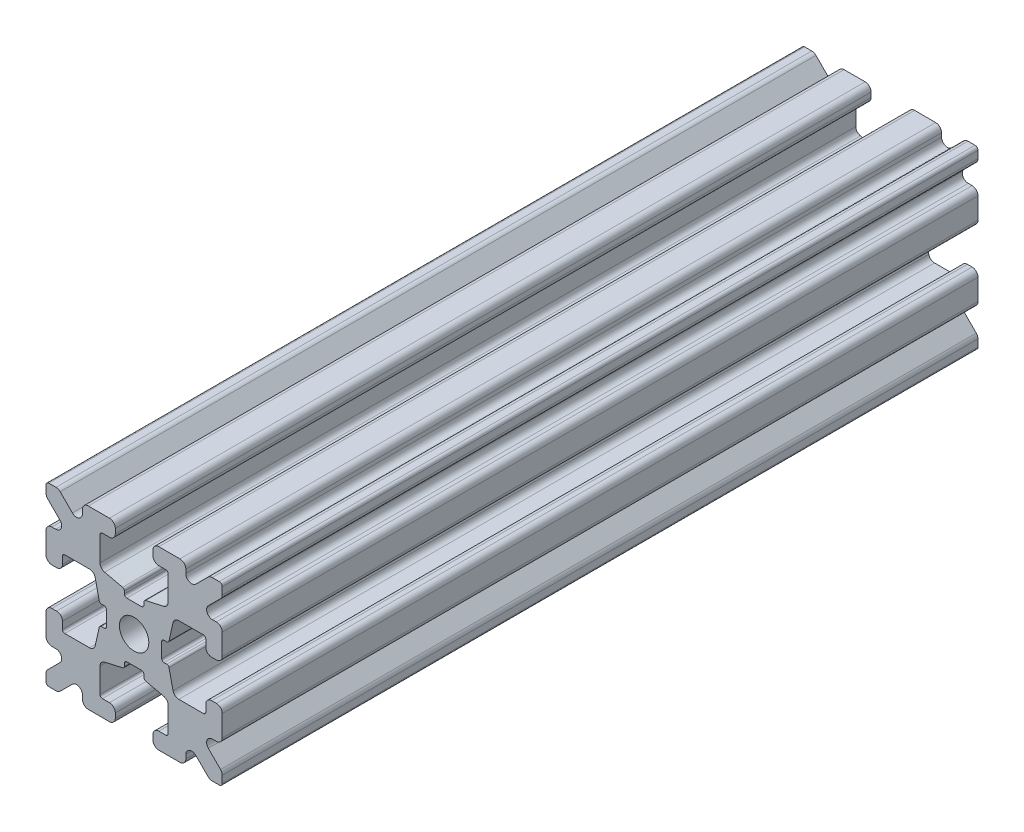
SolidWorks part; units mm, degrees
ref_plane "Front Plane" through (0, 0, 0) normal (0, 0, 1) x (1, 0, 0)
ref_plane "Top Plane" through (0, 0, 0) normal (0, 1, 0) x (1, 0, 0)
ref_plane "Right Plane" through (0, 0, 0) normal (1, 0, 0) x (0, 0, -1)
sketch "Sketch1" plane through (0, 0, 0) normal (0, 0, 1) x (1, 0, 0)
  line L1 (-7.5, -7.5) -> (7.5, -7.5)
  line L2 (-7.5, -7.5) -> (-7.5, 7.5)
  line L3 (-7.5, 7.5) -> (7.5, 7.5)
  line L4 (7.5, -7.5) -> (7.5, 7.5)
  line L5 (-7.5, -7.5) -> (7.5, 7.5) construction
  line L6 (-7.5, 7.5) -> (7.5, -7.5) construction
  circle A0 centre (0, 0) radius 1.25
  point P0 (0, 0)
  dimension "D2" = 2.5
  dimension "D1" = 15
extrude "Boss-Extrude1" add sketch "Sketch1" along normal mid plane 64.328
fillet "Fillet1" radius 0.25 4 edges at (7.5, -7.5, 0) (-7.5, -7.5, 0) (7.5, 7.5, 0) (-7.5, 7.5, 0)
sketch "Sketch2" plane through (0, 0, 32.164) normal (0, 0, 1) x (1, 0, 0)
  line L0 (-7.5, 7.25) -> (-7.5, -7.25) construction
  line L1 (-7.5, 1.6) -> (-6.1, 1.6)
  line L2 (-7.5, 1.6) -> (-7.5, -1.6)
  line L3 (-7.5, -1.6) -> (-6.1, -1.6)
  line L4 (-6.1, 1.6) -> (-6.1, 2.9)
  line L5 (0, 0) -> (-12.1036, 0) construction
  line L6 (-6.1, -2.9) -> (-3.4, -2.9)
  line L7 (0, 0) -> (-7.25, 7.25) construction
  line L8 (-6.1, 2.9) -> (-3.4, 2.9)
  line L9 (-3.4, -2.9) -> (-3.4, 2.9)
  line L10 (55, 0) -> (-55, 0) construction
  line L11 (-6.1, -2.9) -> (-6.1, -1.6)
  line L12 (2.9, 6.1) -> (1.6, 6.1)
  line L13 (2.9, 3.4) -> (-2.9, 3.4)
  line L14 (-2.9, 6.1) -> (-2.9, 3.4)
  line L15 (2.9, 6.1) -> (2.9, 3.4)
  line L16 (-1.6, 6.1) -> (-2.9, 6.1)
  line L17 (1.6, 7.5) -> (1.6, 6.1)
  line L18 (-1.6, 7.5) -> (1.6, 7.5)
  line L19 (-1.6, 7.5) -> (-1.6, 6.1)
  line L20 (-1.6, -7.5) -> (-1.6, -6.1)
  line L21 (-1.6, -7.5) -> (1.6, -7.5)
  line L22 (1.6, -7.5) -> (1.6, -6.1)
  line L23 (-1.6, -6.1) -> (-2.9, -6.1)
  line L24 (2.9, -6.1) -> (2.9, -3.4)
  line L25 (-2.9, -6.1) -> (-2.9, -3.4)
  line L26 (2.9, -3.4) -> (-2.9, -3.4)
  line L27 (2.9, -6.1) -> (1.6, -6.1)
  line L28 (6.1, -2.9) -> (6.1, -1.6)
  line L29 (3.4, -2.9) -> (3.4, 2.9)
  line L30 (6.1, 2.9) -> (3.4, 2.9)
  line L31 (6.1, -2.9) -> (3.4, -2.9)
  line L32 (6.1, 1.6) -> (6.1, 2.9)
  line L33 (7.5, -1.6) -> (6.1, -1.6)
  line L34 (7.5, 1.6) -> (7.5, -1.6)
  line L35 (7.5, 1.6) -> (6.1, 1.6)
  dimension "D1" = 3.2
  dimension "D2" = 5.8
  dimension "D3" = 1.4
  dimension "D4" = 2.7
extrude "Cut-Extrude1" cut sketch "Sketch2" against normal through all
sketch "Sketch4" plane through (0, 0, 32.164) normal (0, 0, 1) x (1, 0, 0)
  line L0 (-3.4, 2.9) -> (-2.75, 0)
  line L1 (55, 0) -> (-55, 0) construction
  line L2 (-2.75, 0) -> (-3.4, -2.9)
  line L3 (-3.4, -2.9) -> (-3.4, 2.9) construction
  line L4 (-3.4, 2.9) -> (-3.4, -2.9)
  line L5 (-2.9, 3.4) -> (0, 2.75)
  line L6 (0, 2.75) -> (2.9, 3.4)
  line L7 (2.9, 3.4) -> (-2.9, 3.4)
  line L8 (3.4, 2.9) -> (2.75, 0)
  line L9 (2.75, 0) -> (3.4, -2.9)
  line L10 (3.4, -2.9) -> (3.4, 2.9)
  line L11 (-2.9, -3.4) -> (0, -2.75)
  line L12 (0, -2.75) -> (2.9, -3.4)
  line L13 (2.9, -3.4) -> (-2.9, -3.4)
  circle A2 centre (0, 0) radius 2.75
  circle A3 centre (0, 0) radius 2.75 construction
  dimension "D1" = 1.5
extrude "Cut-Extrude3" cut sketch "Sketch4" against normal through all
fillet "Fillet3" radius 0.5 16 edges at (-6.1, -1.6, 0) (-7.5, -1.6, 0) (-6.1, 1.6, 0) (-7.5, 1.6, 0) (-1.6, -7.5, 0) (-1.6, -6.1, 0) (1.6, -7.5, 0) (1.6, -6.1, 0) (6.1, -1.6, 0) (7.5, -1.6, 0) (7.5, 1.6, 0) (6.1, 1.6, 0) (1.6, 7.5, 0) (1.6, 6.1, 0) (-1.6, 7.5, 0) (-1.6, 6.1, 0)
fillet "Fillet4" radius 0.5 8 edges at (-3.4, 2.9, 0) (-3.4, -2.9, 0) (2.9, -3.4, 0) (-2.9, -3.4, 0) (3.4, -2.9, 0) (3.4, 2.9, 0) (-2.9, 3.4, 0) (2.9, 3.4, 0)
fillet "Fillet5" radius 3 4 edges at (0, -2.75, 0) (2.75, 0, 0) (-2.75, 0, 0) (0, 2.75, 0)
fillet "Fillet6" radius 0.2 8 edges at (-2.9, -6.1, 0) (2.9, -6.1, 0) (6.1, -2.9, 0) (6.1, 2.9, 0) (2.9, 6.1, 0) (-2.9, 6.1, 0) (-6.1, -2.9, 0) (-6.1, 2.9, 0)
sketch "Sketch5" plane through (0, 0, 32.164) normal (0, 0, 1) x (1, 0, 0)
  line L0 (0, 0) -> (-7.25, 7.25) construction
  line L1 (-7.5, 6.4393) -> (-5.4607, 4.4)
  line L2 (-6.4393, 7.5) -> (-4.4, 5.4607)
  line L3 (-7.5, 4.4) -> (-5.4607, 4.4)
  line L4 (-3.8003, 2.9) -> (-5.9, 2.9) construction
  line L5 (0, 0) -> (-12.1819, 0) construction
  line L6 (-4.4, 7.5) -> (-4.4, 5.4607)
  line L7 (-2.9, 5.9) -> (-2.9, 3.8003) construction
  line L8 (-7.5, 6.4393) -> (-7.5, 4.4)
  line L9 (-7.5, 7.25) -> (-7.5, 2.1) construction
  line L10 (2.1, -7.5) -> (7.25, -7.5) construction
  line L11 (7.5, -7.25) -> (7.5, -2.1) construction
  line L12 (7.25, 7.5) -> (2.1, 7.5) construction
  line L13 (-2.1, 7.5) -> (-7.25, 7.5) construction
  line L14 (-4.4, 7.5) -> (-6.4393, 7.5)
  line L16 (55, 0) -> (-55, 0) construction
  line L17 (0, 0) -> (0, 10.993) construction
  line L18 (0, -54.6431) -> (0, 54.6431) construction
  line L20 (4.4, 7.5) -> (6.4393, 7.5)
  line L22 (7.5, 6.4393) -> (7.5, 4.4)
  line L23 (4.4, 7.5) -> (4.4, 5.4607)
  line L24 (7.5, 4.4) -> (5.4607, 4.4)
  line L25 (6.4393, 7.5) -> (4.4, 5.4607)
  line L26 (7.5, 6.4393) -> (5.4607, 4.4)
  line L27 (7.5, -6.4393) -> (5.4607, -4.4)
  line L28 (6.4393, -7.5) -> (4.4, -5.4607)
  line L29 (7.5, -4.4) -> (5.4607, -4.4)
  line L30 (4.4, -7.5) -> (4.4, -5.4607)
  line L31 (7.5, -6.4393) -> (7.5, -4.4)
  line L33 (4.4, -7.5) -> (6.4393, -7.5)
  line L36 (-4.4, -7.5) -> (-6.4393, -7.5)
  line L38 (-7.5, -6.4393) -> (-7.5, -4.4)
  line L39 (-4.4, -7.5) -> (-4.4, -5.4607)
  line L40 (-7.5, -4.4) -> (-5.4607, -4.4)
  line L41 (-6.4393, -7.5) -> (-4.4, -5.4607)
  line L42 (-7.5, -6.4393) -> (-5.4607, -4.4)
  dimension "D1" = 1.5
  dimension "D2" = 1.5
  dimension "D3" = 1.5
extrude "Cut-Extrude4" cut sketch "Sketch5" against normal through all
fillet "Fillet8" radius 0.5 24 edges at (-5.4607, 4.4, 0) (-7.5, 4.4, 0) (-5.4607, -4.4, 0) (-7.5, -4.4, 0) (-4.4, -7.5, 0) (-4.4, -5.4607, 0) (4.4, -7.5, 0) (4.4, -5.4607, 0) (5.4607, -4.4, 0) (7.5, -4.4, 0) (7.5, 4.4, 0) (5.4607, 4.4, 0) (4.4, 5.4607, 0) (4.4, 7.5, 0) (-4.4, 5.4607, 0) (-4.4, 7.5, 0) (-6.4393, 7.5, 0) (-7.5, 6.4393, 0) (6.4393, 7.5, 0) (7.5, 6.4393, 0) (6.4393, -7.5, 0) (7.5, -6.4393, 0) (-6.4393, -7.5, 0) (-7.5, -6.4393, 0)
sketch "Sketch6" plane through (0, 0, 32.164) normal (0, 0, 1) x (1, 0, 0)
  line L0 (0, 0) -> (0, 11.013) construction
  line L1 (0.6561, 2.8971) -> (2.1235, 2.8971) construction
  line L2 (0, -54.6431) -> (0, 54.6431) construction
  line L3 (0, 0) -> (7.25, 7.25) construction
  line L4 (7.5, 0.8255) -> (7.5, -0.8255)
  line L5 (2.3471, 0.8255) -> (7.5, 0.8255)
  line L6 (0, 0) -> (12.4016, 0) construction
  line L7 (0.8255, -7.5) -> (-0.8255, -7.5)
  line L8 (2.3471, -0.8255) -> (2.3471, 0.8255)
  line L9 (0.8255, -2.3471) -> (0.8255, -7.5)
  line L10 (7.5, -0.8255) -> (2.3471, -0.8255)
  line L11 (-7.5, -0.8255) -> (-2.3471, -0.8255)
  line L12 (-2.3471, -0.8255) -> (-2.3471, 0.8255)
  line L13 (-0.8255, -2.3471) -> (0.8255, -2.3471)
  line L14 (-0.8255, 7.5) -> (-0.8255, 2.3471)
  line L15 (-0.8255, 2.3471) -> (0.8255, 2.3471)
  line L16 (-0.8255, -7.5) -> (-0.8255, -2.3471)
  line L17 (0.8255, 2.3471) -> (0.8255, 7.5)
  line L18 (0.8255, 7.5) -> (-0.8255, 7.5)
  line L19 (3.9, 7.5) -> (2.1, 7.5) construction
  line L20 (-2.3471, 0.8255) -> (-7.5, 0.8255)
  line L21 (-7.5, 0.8255) -> (-7.5, -0.8255)
  point P5 (0, -2.5973)
  point P7 (0, 2.5973)
  dimension "D3" = 0.55
  dimension "D1" = 1.651
extrude "Cut-Extrude5" cut sketch "Sketch6" against normal through all
fillet "Fillet10" radius 0.2 16 edges at (-2.935, 0.8255, 0) (-2.935, -0.8255, 0) (2.935, -0.8255, 0) (2.935, 0.8255, 0) (0.8255, 2.935, 0) (-0.8255, 2.935, 0) (-2.3471, 0.8255, 0) (-2.3471, -0.8255, 0) (0.8255, 2.3471, 0) (-0.8255, 2.3471, 0) (2.3471, 0.8255, 0) (2.3471, -0.8255, 0) (0.8255, -2.935, 0) (0.8255, -2.3471, 0) (-0.8255, -2.3471, 0) (-0.8255, -2.935, 0)
